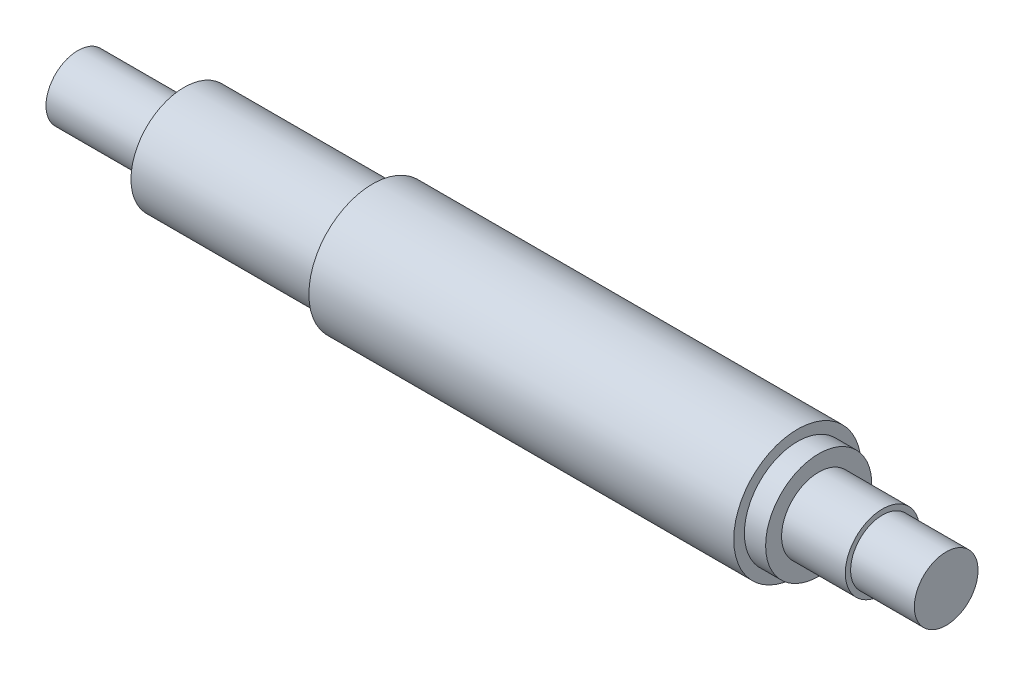
SolidWorks part; units mm, degrees
ref_plane "Front Plane" through (0, 0, 0) normal (0, 0, 1) x (1, 0, 0)
ref_plane "Top Plane" through (0, 0, 0) normal (0, 1, 0) x (1, 0, 0)
ref_plane "Right Plane" through (0, 0, 0) normal (1, 0, 0) x (0, 0, -1)
sketch "Sketch2" plane through (0, 0, 0) normal (0, 0, 1) x (1, 0, 0)
  line L0 (-40.875, 0) -> (40.875, 0)
  line L1 (-40.875, 0) -> (-40.875, 3)
  line L2 (-40.875, 3) -> (-30.875, 3)
  line L3 (-13.125, 5) -> (-13.125, 6)
  line L4 (-13.125, 6) -> (26.875, 6)
  line L5 (26.875, 6) -> (26.875, 5)
  line L6 (-30.875, 3) -> (-30.875, 5)
  line L7 (-30.875, 5) -> (-13.125, 5)
  line L8 (26.875, 5) -> (28.875, 5)
  line L9 (28.875, 5) -> (28.875, 3.5)
  line L10 (28.875, 3.5) -> (34.875, 3.5)
  line L11 (34.875, 3.5) -> (34.875, 3)
  line L13 (34.875, 3) -> (40.875, 3)
  line L14 (40.875, 3) -> (40.875, 0)
  point P1 (28.875, 3.5011)
  point P5 (0, 0)
  point P12 (40.5918, 0)
  point P18 (0, 0)
  dimension "D2" = 6
  dimension "D3" = 3
  dimension "D4" = 10
  dimension "D5" = 27.75
  dimension "D6" = 40
  dimension "D7" = 6
  dimension "D8" = 2
  dimension "D9" = 5
  dimension "D11" = 5
  dimension "D12" = 6
  dimension "D10" = 3.5
  dimension "D13" = 3
revolve "Revolve1" add sketch "Sketch2" angle 360 about L0
sketch "Sketch3" [suppressed] plane through (0, 0, 0) normal (0, 0, 1) x (1, 0, 0)
  line L0 (-43.375, 0) -> (43.375, 0)
  line L1 (-43.375, 0) -> (-43.375, 3)
  line L2 (-43.375, 3) -> (-33.375, 3)
  line L3 (-20.625, 5) -> (-20.625, 7.5)
  line L4 (-20.625, 7.5) -> (29.375, 7.5)
  line L5 (29.375, 7.5) -> (29.375, 5)
  line L6 (-33.375, 3) -> (-33.375, 5)
  line L7 (-33.375, 5) -> (-20.625, 5)
  line L8 (29.375, 5) -> (31.375, 5)
  line L9 (31.375, 5) -> (31.375, 3.5)
  line L10 (31.375, 3.5) -> (37.375, 3.5)
  line L11 (43.375, 3) -> (43.375, 0)
  line L13 (4.375, 7.5) -> (4.375, 16.7852) construction
  line L14 (37.375, 3.5) -> (37.375, 3)
  line L15 (37.375, 3) -> (43.375, 3)
  point P4 (0, 0)
  point P17 (29.375, 6.25)
  dimension "D12" = 6
  dimension "D2" = 7.5
  dimension "D4" = 3
  dimension "D1" = 10
  dimension "D8" = 5
  dimension "D10" = 5
  dimension "D3" = 50
  dimension "D5" = 22.75
  dimension "D7" = 2
  dimension "D6" = 3.5
  dimension "D9" = 3
  dimension "D11" = 6
revolve "Revolve2" [suppressed] add sketch "Sketch3" angle 360 about L0
equation "\"mini-flipper-shaft-diameter\"= 26mm"
equation "\"mini-shaft-ring-groove-diam\"= 7.8mm"
equation "\"mini-shaft-ring-groove-width\"= 1mm"
equation "\"dtCoverPlate-DistFrom-GearCent\"= 73mm"
equation "\"wormGearShaft-L\"= \"dtCoverPlate-DistFrom-GearCent\" - 27.75 + 3.75"
equation "\"wormGearShaft-Dsmall\"= 6mm"
equation "\"wormGearShaft-Dworm\"= 12mm"
equation "\"D3@Sketch2\"=\"wormGearShaft-Dsmall\"/2"
equation "\"D4@Sketch3\"=\"wormGearShaft-Dsmall\"/2"
equation "\"wormL-D\" = 12mm"
equation "\"wormR-D\" = 15mm"
equation "\"wormGearL-D\" = 40mm"
equation "\"wormGearR-D\" = 50mm"
equation "\"D5@Sketch3\"=73-\"wormGearR-D\"/2 - 17.25-8"
equation "\"D5@Sketch2\"=73-\"wormGearL-D\"/2 -17.25-8"
